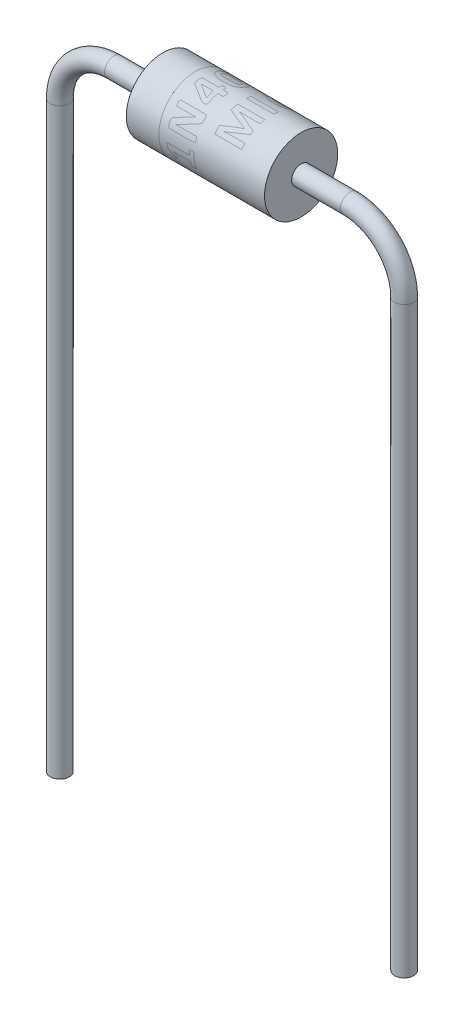
SolidWorks part; units mm, degrees
other "Diode"
other "Cathode Silver Band"
other "Wire"
ref_plane "Front Plane" through (0, 0, 0) normal (0, 0, 1) x (1, 0, 0)
ref_plane "Top Plane" through (0, 0, 0) normal (0, 1, 0) x (1, 0, 0)
ref_plane "Right Plane" through (0, 0, 0) normal (1, 0, 0) x (0, 0, -1)
sketch "Sketch1" plane through (0, 0, 0) normal (1, 0, 0) x (0, 0, -1)
  circle A0 centre (0, 0) radius 1.35
  circle A1 centre (0, 0) radius 0.35
  dimension "D1" = 2.7
  dimension "D2" = 0.7
extrude "Boss-Extrude1" add sketch "Sketch1" along normal mid plane 5.1
sketch "Sketch2" plane through (-2.55, 0, 0) normal (-1, 0, 0) x (0, 0, 1)
  circle A1 centre (0, 0) radius 1.35 construction
  circle A2 centre (0, 0) radius 1.34
  circle A3 centre (0, 0) radius 1.34
  circle A4 centre (0, 0) radius 1.35
  dimension "D1" = 0.01
extrude "Cut-Extrude1" cut sketch "Sketch2" against normal blind 1.2
sketch "Sketch3" plane through (-1.35, 0, 0) normal (-1, 0, 0) x (0, 0, 1)
  circle A0 centre (0, 0) radius 1.34 construction
  circle A1 centre (0, 0) radius 1.34
  circle A2 centre (0, 0) radius 1.35 construction
  circle A3 centre (0, 0) radius 1.35
extrude "Boss-Extrude2" add sketch "Sketch3" along normal up to surface (1.2 mm away) separate body up to face at (-2.55, 0, -0.35)
ref_plane "Plane1" through (0, 5, 0) normal (0, 1, 0) x (1, 0, 0)
sketch "Sketch4" plane through (0, 5, 0) normal (0, 1, 0) x (1, 0, 0)
  line L0 (-0.05, 7.5) -> (-0.05, -7.5) construction
  line L1 (-0.05, 0) -> (-2.55, 0) construction
  line L2 (-2.55, 1.35) -> (-2.55, -1.35) construction
  line L4 (-0.05, 0) -> (1.45, 0) construction
  line L5 (1.45, 7.5) -> (1.45, -7.5) construction
  text T0 "1N4001" font "Calibri" height 1
  text T1 "MIC" font "Corbel" height 1
  dimension "D1" = 2.5
  dimension "D2" = 15
  dimension "D3" = 1.5
wrap "Wrap1" sketch "Sketch4" wrap type scribe source sketch "Sketch4" face at (2.55, 0, -1.35)
sketch "Sketch5" plane through (0, 0, 0) normal (0, 0, 1) x (1, 0, 0)
  line L0 (0, 0) -> (-4.35, 0)
  line L1 (-6.35, -2) -> (-6.35, -23.5084)
  line L2 (0, 0) -> (4.35, 0)
  line L3 (6.35, -2) -> (6.35, -23.5084)
  arc A0 (-4.35, 0) -> (-6.35, -2) centre (-4.35, -2) ccw
  arc A1 (4.35, 0) -> (6.35, -2) centre (4.35, -2) cw
  dimension "D2" = 2
  dimension "D3" = 58
  dimension "D1" = 12.7
sketch "Sketch6" plane through (0, 0, 0) normal (1, 0, 0) x (0, 0, -1)
  circle A0 centre (0, 0) radius 0.35
  dimension "D1" = 0.7
sweep "Sweep1" add profiles "Sketch6" path "Sketch5"
